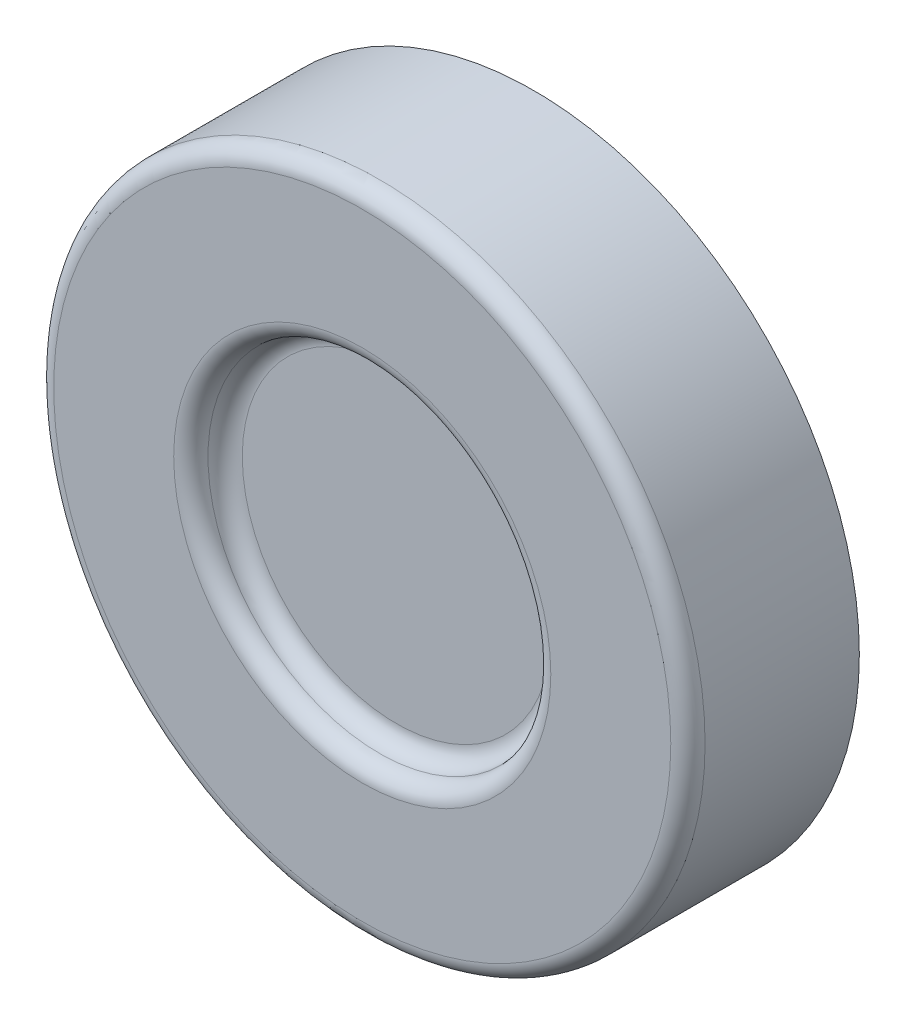
SolidWorks part; units mm, degrees
ref_plane "Front Plane" through (0, 0, 0) normal (0, 0, 1) x (1, 0, 0)
ref_plane "Top Plane" through (0, 0, 0) normal (0, 1, 0) x (1, 0, 0)
ref_plane "Right Plane" through (0, 0, 0) normal (1, 0, 0) x (0, 0, -1)
sketch "Sketch1" plane through (0, 0, 0) normal (0, 0, 1) x (1, 0, 0)
  circle A0 centre (0, 0) radius 19
  dimension "D1" = 38
extrude "Boss-Extrude1" add sketch "Sketch1" along normal blind 10
sketch "Sketch2" plane through (0, 0, 10) normal (0, 0, 1) x (1, 0, 0)
  circle A0 centre (0, 0) radius 10
  dimension "D1" = 20
extrude "Cut-Extrude1" cut sketch "Sketch2" against normal blind 2
fillet "Fillet1" radius 1 3 edges at (10, 0, 8) (10, 0, 10) (19, 0, 10)
